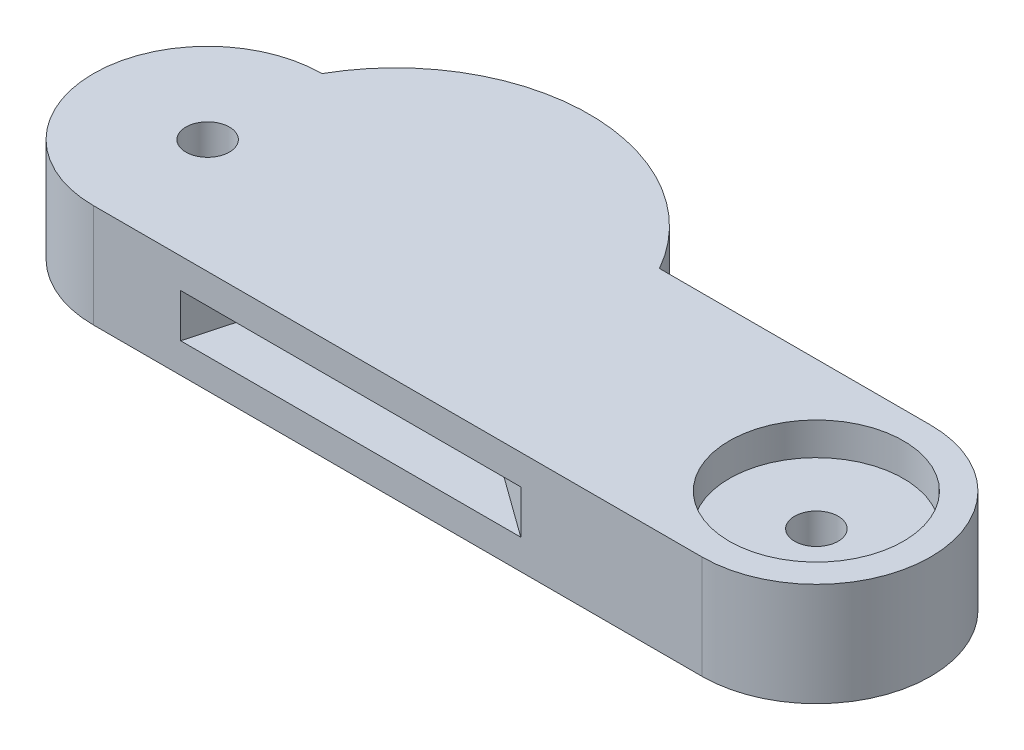
SolidWorks part; units mm, degrees
ref_plane "Front Plane" through (0, 0, 0) normal (0, 0, 1) x (1, 0, 0)
ref_plane "Top Plane" through (0, 0, 0) normal (0, 1, 0) x (1, 0, 0)
ref_plane "Right Plane" through (0, 0, 0) normal (1, 0, 0) x (0, 0, -1)
sketch "Sketch1" plane through (0, 0, 0) normal (0, 1, 0) x (1, 0, 0)
  line L0 (0, -10.5004) -> (-55.9305, -10.5004)
  line L1 (0, 10.5004) -> (-55.9305, 10.5004)
  line L5 (0, 11.5004) -> (-55.9305, 11.5004) construction
  line L6 (0, -11.5004) -> (-55.9305, -11.5004) construction
  circle A0 centre (0, 0) radius 2
  arc A1 (0, -10.5004) -> (0, 10.5004) centre (0, 0) ccw
  arc A2 (-55.9305, 10.5004) -> (-55.9305, -10.5004) centre (-55.9305, 0) ccw
  circle A3 centre (-55.9305, 0) radius 2
  arc A5 (-65.61, 15.5646) -> (-64.0333, -21.1346) centre (0, 0) ccw construction
  arc A6 (-64.0333, -21.1346) -> (-49.5078, -28.451) centre (-53.1123, -17.5301) ccw construction
  arc A7 (0, -11.5004) -> (0, 11.5004) centre (0, 0) ccw construction
  arc A8 (-55.9305, 11.5004) -> (-55.9305, -11.5004) centre (-55.9305, 0) ccw construction
  arc A10 (-55.9305, 10.5004) -> (-55.9305, -10.5004) centre (-55.9305, 0) ccw construction
  circle A11 centre (0, 0) radius 67.4309 construction
  dimension "D1" = 4
  dimension "D2" = 1
  dimension "D3" = 4
extrude "Boss-Extrude1" add sketch "Sketch1" along normal mid plane 9.5
sketch "Sketch3" plane through (0, 0, 0) normal (0, 1, 0) x (1, 0, 0)
  line L0 (0, 0) -> (-47.1525, -15.3208) construction
  line L1 (0, 0) -> (24.7895, -42.9367) construction
  line L2 (0, 0) -> (-55.9305, 0) construction
  line L3 (24.7895, -42.9367) -> (-41.5934, 5.0595) construction
  line L4 (-41.5934, 5.0595) -> (-47.1525, -15.3208) construction
  line L5 (-41.5934, 5.0595) -> (-37.6461, 19.5308) construction
  line L6 (-41.5934, 5.0595) -> (-53.749, 13.8482) construction
  line L7 (22.8477, -44.0007) -> (-38.0092, 0) construction
  line L8 (-35.7518, 18.8753) -> (-39.2995, 5.869)
  line L9 (-43.8873, 4.25) -> (-54.8123, 12.149)
  line L11 (26.6452, -41.8104) -> (-39.2995, 5.869)
  line L12 (-39.6108, 19.9279) -> (-42.7627, 8.3729) construction
  line L13 (-42.7627, 8.3729) -> (-52.4686, 15.3905) construction
  line L14 (-40.9004, 0) -> (-45.9674, -18.5763) construction
  line L15 (-43.8873, 4.25) -> (-48.2065, -11.585)
  line L18 (-40.4216, 6.6802) -> (-50.8477, 14.2185) construction
  line L20 (-41.5934, 5.0595) -> (-52.0196, 12.5978) construction
  line L21 (-42.7652, 3.4387) -> (-53.1914, 10.977) construction
  line L23 (-43.5229, 5.5858) -> (-49.082, -14.7945) construction
  line L26 (-39.6639, 4.5332) -> (-45.223, -15.8471) construction
  line L27 (25.9613, -41.316) -> (-40.4216, 6.6802) construction
  line L28 (23.6177, -44.5574) -> (-42.7652, 3.4387) construction
  arc A1 (-48.2065, -11.585) -> (26.6452, -41.8104) centre (0, 0) ccw
  arc A4 (-55.9305, 10.5004) -> (-55.9305, -10.5004) centre (-55.9305, 0) ccw construction
  arc A7 (-35.7518, 18.8753) -> (-54.8123, 12.149) centre (-41.5934, 5.0595) ccw
  dimension "D1" = 99.1581
  dimension "D3" = 120
  dimension "D6" = 30
  dimension "D2" = 18
  dimension "D4" = 2
  dimension "D5" = 2
extrude "Cut-Extrude1" cut sketch "Sketch3" against normal mid plane 4
sketch "Sketch5" plane through (0, 0, 0) normal (0, 1, 0) x (1, 0, 0)
  line L0 (-40.4241, 1.7461) -> (-52.5322, 10.5004) construction
  line L1 (-40.4241, 1.7461) -> (-35.7382, 18.9254) construction
  line L2 (-52.5322, 10.5004) -> (-43.8873, 4.25) construction
  line L3 (-39.2995, 5.869) -> (-38.0362, 10.5004) construction
  line L4 (-55.9305, 10.5004) -> (-24.9177, 10.5004)
  line L5 (0, 10.5004) -> (-55.9305, 10.5004) construction
  circle A0 centre (-40.4241, 1.7461) radius 17.807
extrude "Boss-Extrude2" add sketch "Sketch5" along normal up to surface and the other way up to surface contours A0 region at (-40.4241, 0, -14.2141) up to face at (0, 4.75, 2) other way up to face at (-27.9653, -4.75, 0)
sketch "Sketch6" plane through (0, 0, 0) normal (0, 1, 0) x (1, 0, 0)
  line L0 (-39.2995, 5.869) -> (-16.6593, -10.5004)
  line L1 (-47.9107, -10.5004) -> (-43.8873, 4.25)
  line L2 (-43.8873, 4.25) -> (-54.8544, 12.1794)
  line L3 (-39.2995, 5.869) -> (-35.7382, 18.9254)
  line L4 (-16.6593, -10.5004) -> (-39.2995, 5.869) construction
  line L5 (-43.8873, 4.25) -> (-47.9107, -10.5004) construction
  line L6 (-52.5322, 10.5004) -> (-43.8873, 4.25) construction
  line L7 (-39.2995, 5.869) -> (-38.0362, 10.5004) construction
  line L8 (-55.9305, -10.5004) -> (0, -10.5004) construction
  line L9 (-16.6593, -10.5004) -> (-47.9107, -10.5004)
  arc A0 (-24.9177, 10.5004) -> (-55.9305, 10.5004) centre (-40.4241, 1.7461) ccw construction
  arc A1 (-35.7382, 18.9254) -> (-54.8544, 12.1794) centre (-40.4241, 1.7461) ccw
extrude "Cut-Extrude2" cut sketch "Sketch6" against normal mid plane 4
sketch "Sketch7" plane through (0, 4.75, 0) normal (0, 1, 0) x (1, 0, 0)
  circle A0 centre (0, 0) radius 8
  dimension "D1" = 16
extrude "Cut-Extrude3" cut sketch "Sketch7" against normal blind 3
ref_plane "Plane1" through (0, 0, 0) normal (0, 1, 0) x (1, 0, 0)
